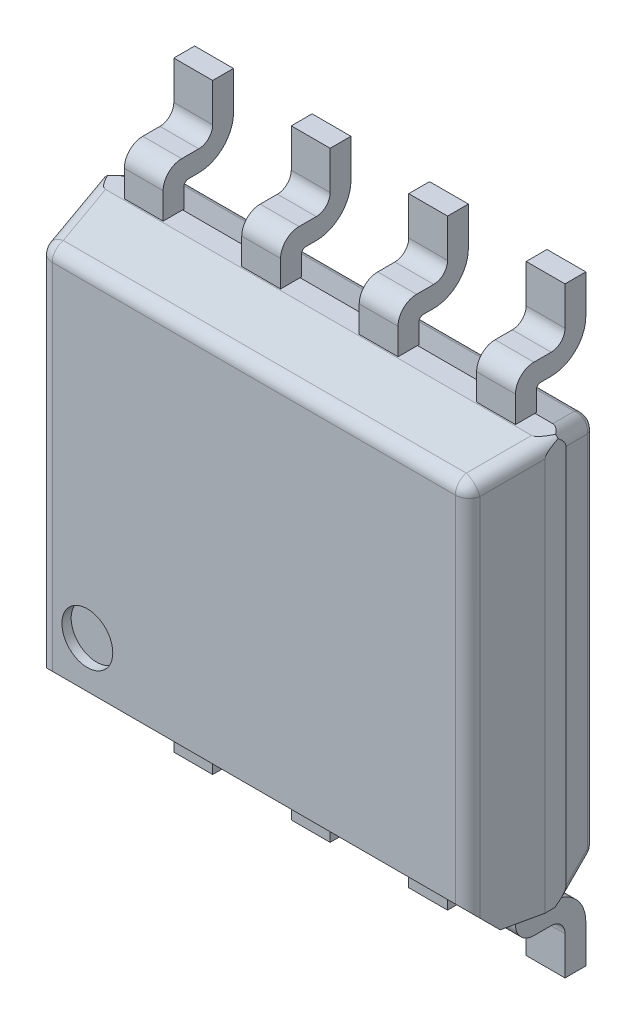
SolidWorks part; units mm, degrees
ref_plane "Front Plane" through (0, 0, 0) normal (0, 0, 1) x (1, 0, 0)
ref_plane "Top Plane" through (0, 0, 0) normal (0, 1, 0) x (1, 0, 0)
ref_plane "Right Plane" through (0, 0, 0) normal (1, 0, 0) x (0, 0, -1)
sketch "Sketch1" plane through (0, 0, 0) normal (0, 0, 1) x (1, 0, 0)
  line L1 (-2.45, 2.2) -> (2.45, 2.2)
  line L2 (-2.45, 2.2) -> (-2.45, -2.2)
  line L3 (-2.45, -2.2) -> (2.45, -2.2)
  line L4 (2.45, 2.2) -> (2.45, -2.2)
  dimension "D1" = 4.9
  dimension "D2" = 4.4
  dimension "D3" = 2.45
  dimension "D4" = 2.2
extrude "Boss-Extrude1" add sketch "Sketch1" along normal blind 1.375
chamfer "Chamfer1" distance 0.3 angle 45 1 edges at (0, -2.2, 1.375)
chamfer "Chamfer2" distance 0.15 distance2 0.45 1 edges at (0, -2.2, 0) first distance on face at (0, 0, 0)
chamfer "Chamfer7" distance 0.15 distance2 0.45 1 edges at (2.45, 0.075, 0) first distance on face at (0, 0.075, 0)
chamfer "Chamfer8" distance 0.15 distance2 0.45 1 edges at (-2.45, 0.075, 0) first distance on face at (-0.075, 0.075, 0)
fillet "Fillet1" radius 0.15 1 edges at (0, -2.05, 0)
chamfer "Chamfer3" distance 0.15 distance2 0.45 1 edges at (0, 2.2, 0) first distance on face at (0, 0.1291, 0)
chamfer "Chamfer6" distance 0.7 distance2 0.15 1 edges at (2.45, 0.15, 1.375) first distance on face at (2.45, -0.38, 0.945)
fillet "Fillet2" radius 0.15 1 edges at (0, 2.05, 0)
chamfer "Chamfer4" distance 0.7 distance2 0.15 1 edges at (-0.075, 2.2, 1.375) first distance on face at (0.46, 2.2, 0.865)
sketch "Sketch2" plane through (0, 0, 1.375) normal (0, 0, 1) x (1, 0, 0)
  line L0 (-2.45, 2.05) -> (-2.45, -1.9) construction
  line L1 (2.3643, -2.2) -> (-2.45, -2.2) construction
  circle A0 centre (-1.8, -1.4) radius 0.275
  dimension "D3" = 0.55
  dimension "D1" = 0.65
  dimension "D2" = 0.8
extrude "Cut-Extrude1" cut sketch "Sketch2" against normal blind 0.1
chamfer "Chamfer5" distance 0.7 distance2 0.15 1 edges at (-2.45, 0.075, 1.375) first distance on face at (-2.45, 0.025, 0.9)
fillet "Fillet3" radius 0.15 1 edges at (0, 2.05, 1.375)
fillet "Fillet4" radius 0.15 3 edges at (-2.3877, 2.1377, 0.9657) (-2.3071, 2.023, 1.3416) (-2.3, 0.0144, 1.375)
fillet "Fillet5" radius 0.15 5 edges at (-2.3921, -2.1421, 0.2763) (-2.3094, -2.0296, 0.0283) (-2.3921, 2.1421, 0.2763) (-2.3094, 2.0296, 0.0283) (-2.3, 0, 0)
fillet "Fillet6" radius 0.15 3 edges at (2.3877, 2.1377, 0.9657) (2.3071, 2.023, 1.3416) (2.3, 0.0144, 1.375)
fillet "Fillet7" radius 0.15 5 edges at (2.3921, 2.1421, 0.2763) (2.3094, 2.0296, 0.0283) (2.3921, -2.1421, 0.2763) (2.3094, -2.0296, 0.0283) (2.3, 0, 0)
ref_plane "Plane1" through (-2.115, 0, 0) normal (-1, 0, 0) x (0, 0, 1)
sketch "Sketch3" plane through (-2.115, 0, 0) normal (-1, 0, 0) x (0, 0, 1)
  line L2 (0.45, -2.2) -> (0.5726, -2.2) construction
  line L3 (0.675, -2.2) -> (0.5726, -2.2) construction
  line L4 (0.6605, 2.2) -> (0.4355, 2.2)
  line L6 (0.45, -2.2) -> (0.5726, -2.2)
  line L7 (0.675, -2.2) -> (0.5726, -2.2)
  line L8 (0.675, -2.2) -> (0.45, -2.2)
  line L10 (0.5625, 0) -> (0, 0) construction
  line L11 (0.6605, 2.2) -> (0.6605, 2.485)
  line L12 (0.4605, 2.685) -> (0.275, 2.685)
  line L13 (0.125, 2.835) -> (0.125, 3.25)
  line L14 (0, -1.9419) -> (0, 1.9419) construction
  line L15 (0.4355, 2.2) -> (0.4355, 2.41)
  line L16 (0.4355, 2.46) -> (0.275, 2.46) construction
  line L17 (0.125, 3.25) -> (-0.1, 3.25)
  line L18 (0.3855, 2.46) -> (0.275, 2.46)
  line L19 (-0.1, 2.835) -> (-0.1, 3.25)
  line L20 (0.4355, 2.425) -> (0.4355, 2.46) construction
  line L21 (0.4355, 2.425) -> (0.4355, 2.425) construction
  line L22 (0.4355, 2.425) -> (0.4355, 2.425) construction
  line L24 (0.535, 1.95) -> (0.4355, 2.2) construction
  line L25 (0.6605, 2.2) -> (0.535, 1.95) construction
  arc A0 (0.6605, 2.485) -> (0.4605, 2.685) centre (0.4605, 2.485) ccw
  arc A1 (0.125, 2.835) -> (0.275, 2.685) centre (0.275, 2.835) ccw
  arc A2 (0.4355, 2.41) -> (0.3855, 2.46) centre (0.3855, 2.41) ccw
  arc A3 (-0.1, 2.835) -> (0.275, 2.46) centre (0.275, 2.835) ccw
  arc A4 (0.4355, 2.46) -> (0.4355, 2.46) centre (0.4355, 2.46) ccw construction
  point P6 (0.5625, 2.45)
  point P7 (0.548, 2.2)
  point P20 (0.125, 2.685)
  dimension "D5" = 0.2
  dimension "D6" = 0.15
  dimension "D8" = 0.05
  dimension "D4" = 0.125
extrude "Boss-Extrude2" add sketch "Sketch3" against normal blind 0.42 contours L19 A3 L18 A2 L15 L11 A0 L12 A1 L13 L17 region at (-2.115, 2.6868, 0.2406)
mirror "Mirror1" about plane through (0, 0, 0) normal (0, 1, 0) of "Boss-Extrude2"
pattern_linear "LPattern1" count 4 spacing 1.27 along (1, 0, 0) of "Mirror1", "Boss-Extrude2"
